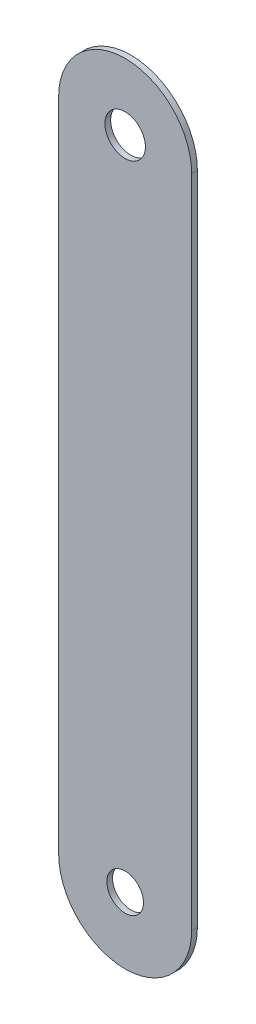
SolidWorks part; units mm, degrees
ref_plane "Front Plane" through (0, 0, 0) normal (0, 0, 1) x (1, 0, 0)
ref_plane "Top Plane" through (0, 0, 0) normal (0, 1, 0) x (1, 0, 0)
ref_plane "Right Plane" through (0, 0, 0) normal (1, 0, 0) x (0, 0, -1)
sketch "Sketch1" plane through (0, 0, 0) normal (0, 0, 1) x (1, 0, 0)
  line L0 (0, 42.1271) -> (0, -42.3756) construction
  line L1 (8.5745, 42.1271) -> (8.5745, -42.3756)
  line L2 (-8.5745, 42.1271) -> (-8.5745, -42.3756)
  arc A0 (8.5745, 42.1271) -> (-8.5745, 42.1271) centre (0, 42.1271) ccw
  arc A1 (-8.5745, -42.3756) -> (8.5745, -42.3756) centre (0, -42.3756) ccw
  circle A2 centre (0, 42.1271) radius 2.6096
  circle A3 centre (0, -42.3756) radius 2.3611
  point P3 (0, -0.1243)
base flange "Base-Flange1" sketch "Sketch1" thickness 0.7366 reverse thickness direction no parameters "D1"=0.7366
sketch "Bend-Lines1" plane through (0, 0, 0) normal (0, 1, 0) x (1, 0, 0)
sketch "Bounding-Box1" plane through (0, 0, 0) normal (0, 1, 0) x (1, 0, 0)
sheet metal parameters "Sheet-Metal1" thickness 0.7366 parameters "D1"=0.7366
flat pattern "Flat-Pattern1" [suppressed]
sketch "Bend-Lines2" plane through (0, 0, 0) normal (0, 1, 0) x (1, 0, 0)
sketch "Bounding-Box2" [suppressed] plane through (0, 0, 0) normal (0, 1, 0) x (1, 0, 0)
